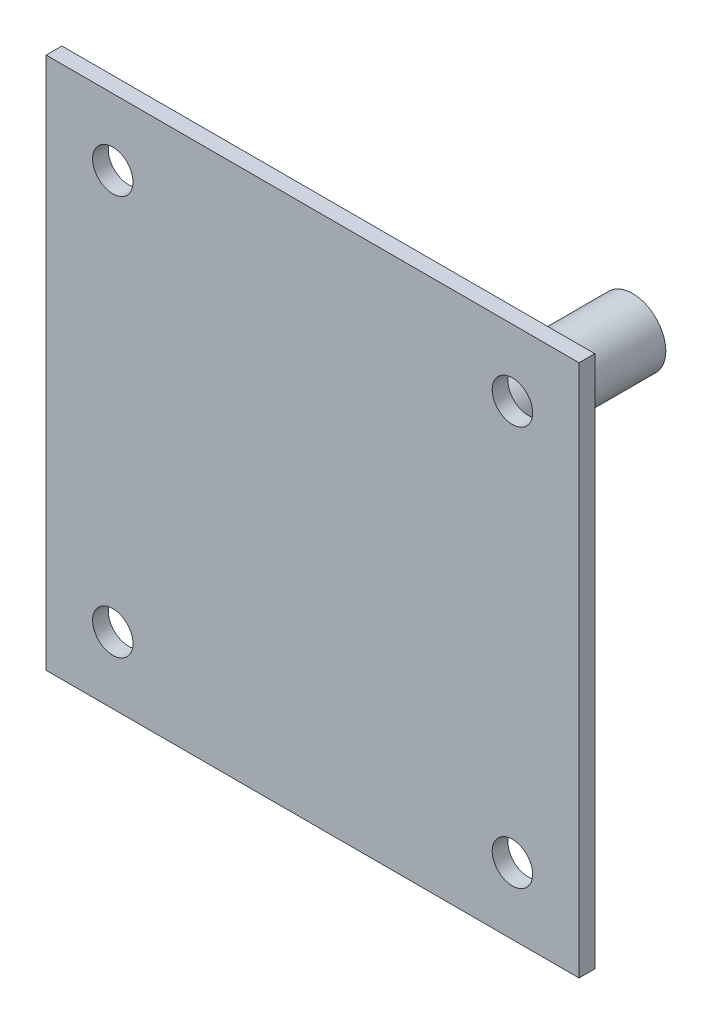
SolidWorks part; units mm, degrees
ref_plane "Front Plane" through (0, 0, 0) normal (0, 0, 1) x (1, 0, 0)
ref_plane "Top Plane" through (0, 0, 0) normal (0, 1, 0) x (1, 0, 0)
ref_plane "Right Plane" through (0, 0, 0) normal (1, 0, 0) x (0, 0, -1)
sketch "Sketch1" plane through (0, 0, 0) normal (0, 0, 1) x (1, 0, 0)
  line L0 (0, 50.8) -> (0, 0) construction
  line L1 (-50.8, 50.8) -> (50.8, 50.8)
  line L2 (-50.8, 50.8) -> (-50.8, -50.8)
  line L3 (-50.8, -50.8) -> (50.8, -50.8)
  line L4 (50.8, 50.8) -> (50.8, -50.8)
  line L5 (-50.8, 50.8) -> (50.8, -50.8) construction
  line L6 (-50.8, -50.8) -> (50.8, 50.8) construction
  line L7 (0, 0) -> (50.8, 0) construction
  circle A0 centre (0, 0) radius 6.35
  circle A1 centre (-38.1, 38.1) radius 3.8564
  circle A2 centre (38.1, 38.1) radius 3.8564
  circle A3 centre (38.1, -38.1) radius 3.8564
  circle A4 centre (-38.1, -38.1) radius 3.8564
  point P0 (0, 0)
  dimension "D1" = 12.7
  dimension "D2" = 12.7
  dimension "D3" = 12.7
  dimension "D4" = 50.8
extrude "Boss-Extrude1" add sketch "Sketch1" along normal blind 3 contours A0 | L4 L1 L2 L3 A2 A1 A0 A3 A4 region at (0, 49.3632, 0) region at (0, 0, 0)
extrude "Boss-Extrude2" add sketch "Sketch1<4>" against normal blind 58 contours A0 region at (0, 0, 0)
sketch "Sketch1<4>" plane through (0, 0, 0) normal (0, 0, 1) x (1, 0, 0) same geometry as "Sketch1"
